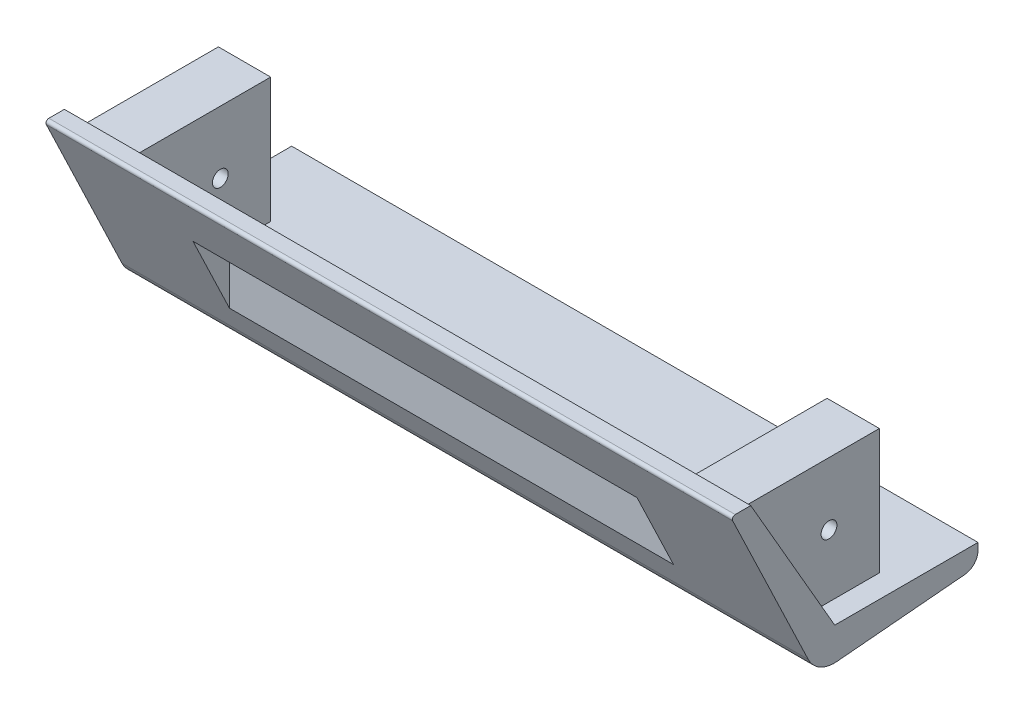
SolidWorks part; units mm, degrees
ref_plane "Front Plane" through (0, 0, 0) normal (0, 0, 1) x (1, 0, 0)
ref_plane "Top Plane" through (0, 0, 0) normal (0, 1, 0) x (1, 0, 0)
ref_plane "Right Plane" through (0, 0, 0) normal (1, 0, 0) x (0, 0, -1)
sketch "Sketch1" plane through (0, 0, 0) normal (1, 0, 0) x (0, 0, -1)
  line L0 (0, 0) -> (-29.3294, 50.8)
  line L1 (0, 0) -> (50, 0)
  line L2 (-29.3294, 50.8) -> (-36.3294, 50.8)
  line L3 (-36.3294, 50.8) -> (-6.2529, -12)
  line L4 (-6.2529, -12) -> (50, -7)
  line L5 (50, -7) -> (50, 0)
  line L6 (-6.2529, -12) -> (-6.2529, 0) construction
  line L7 (-12, 0) -> (0, 0) construction
  dimension "D1" = 50
  dimension "D2" = 60
  dimension "D3" = 50.8
  dimension "D4" = 7
  dimension "D5" = 7
  dimension "D6" = 12
extrude "Boss-Extrude2" add sketch "Sketch1" along normal mid plane 239.55
sketch "Sketch2" plane through (0, 0, 0) normal (0, 0, 1) x (1, 0, 0)
  line L0 (0, 0) -> (0, 50.8) construction
  line L5 (115.75, 47.625) -> (96.7, 47.625) construction
  line L6 (115.75, 47.625) -> (115.75, 3.175) construction
  line L11 (115.75, 3.175) -> (96.7, 3.175) construction
  line L12 (96.7, 47.625) -> (96.7, 3.175) construction
  line L14 (115.35, 47.225) -> (115.35, 3.575)
  line L15 (115.35, 3.575) -> (97.1, 3.575)
  line L28 (97.1, 47.225) -> (97.1, 3.575)
  line L29 (115.35, 47.225) -> (97.1, 47.225)
  line L30 (-96.7, 47.625) -> (-96.7, 3.175) construction
  line L31 (-115.75, 3.175) -> (-96.7, 3.175) construction
  line L32 (-115.75, 47.625) -> (-115.75, 3.175) construction
  line L33 (-115.75, 47.625) -> (-96.7, 47.625) construction
  line L34 (-115.35, 47.225) -> (-97.1, 47.225)
  line L35 (-97.1, 47.225) -> (-97.1, 3.575)
  line L36 (-115.35, 3.575) -> (-97.1, 3.575)
  line L37 (-115.35, 47.225) -> (-115.35, 3.575)
  line L39 (119.775, 0) -> (-119.775, 0) construction
  line L40 (119.775, 50.8) -> (-119.775, 50.8) construction
  line L41 (119.775, 0) -> (119.775, 50.8) construction
  dimension "D2" = 19.05
  dimension "D3" = 44.45
  dimension "D6" = 3.175
  dimension "D4" = 3.175
  dimension "D7" = 4.025
  dimension "D1" = 193.4
  dimension "D5" = 0.4
extrude "Boss-Extrude1" add sketch "Sketch2" along normal up to surface and the other way blind 20 up to face at (0, 25.4, 14.6647)
sketch "Sketch4" plane through (0, 0, 0) normal (1, 0, 0) x (0, 0, -1)
  line L1 (-26.7297, 30.7556) -> (-20, 34.641)
  line L2 (-36.3294, 50.8) -> (-6.2529, -12) construction
  line L3 (0, 0) -> (-29.3294, 50.8) construction
  line L4 (-20, 34.641) -> (-14, 24.2487)
  line L5 (-14, 24.2487) -> (-14, 4.176)
  line L8 (-26.7297, 30.7556) -> (-14, 4.176)
  dimension "D1" = 12
  dimension "D2" = 14
extrude "Cut-Extrude2" cut sketch "Sketch4" against normal mid plane 155
fillet "Fillet1" radius 10 1 edges at (0, -12, 6.2529)
fillet "Fillet2" radius 5 1 edges at (0, -7, -50)
fillet "Fillet3" radius 1 1 edges at (0, 50.8, 36.3294)
hole_wizard "M5 Clearance Hole1" positions "Sketch7" profile "Sketch6" hole size "M5" standard "ANSI Metric" end condition through all
sketch "Sketch7" plane through (115.35, 0, 0) normal (1, 0, 0) x (0, 0, -1)
  line L2 (20, 47.225) -> (20, 3.575) construction
  point P0 (2.4206, 25.4)
  point P14 (20, 25.4)
sketch "Sketch6" plane through (115.35, 25.4, -2.4206) normal (0, 1, 0) x (0, 0, -1)
  line L0 (0, 0) -> (0, 235.125)
  line L1 (0, 235.125) -> (2.75, 235.125)
  line L2 (2.75, 235.125) -> (2.75, 0)
  line L5 (2.75, 0) -> (0, 0)
  line L11 (0, -6.35) -> (0, 107.95) construction
  dimension "Thru Hole Dia." = 5.5
  dimension "Thru Hole Depth" = 235.125
sketch "Sketch8" plane through (77.5, 0, 0) normal (-1, 0, 0) x (0, 0, 1)
  line L0 (20, 34.641) -> (22.5981, 33.141)
  line L1 (20, 34.641) -> (26.7297, 30.7556) construction
  line L2 (22.5981, 33.141) -> (17.5981, 24.4808)
  line L3 (14.866, 23.7487) -> (14, 24.2487)
  line L4 (14, 24.2487) -> (20, 34.641) construction
  line L5 (20, 34.641) -> (14, 24.2487)
  arc A0 (17.5981, 24.4808) -> (14.866, 23.7487) centre (15.866, 25.4808) cw
  dimension "D2" = 2
  dimension "D1" = 3
extrude "Cut-Extrude3" cut sketch "Sketch8" against normal blind 10
equation "\"D1@Sketch2\"=187.05mm+0.25in"
equation "\"RailSpacing\"= 188.75mm"
equation "\"D1@Boss-Extrude2\"=\"RailSpacing\"+2in"
